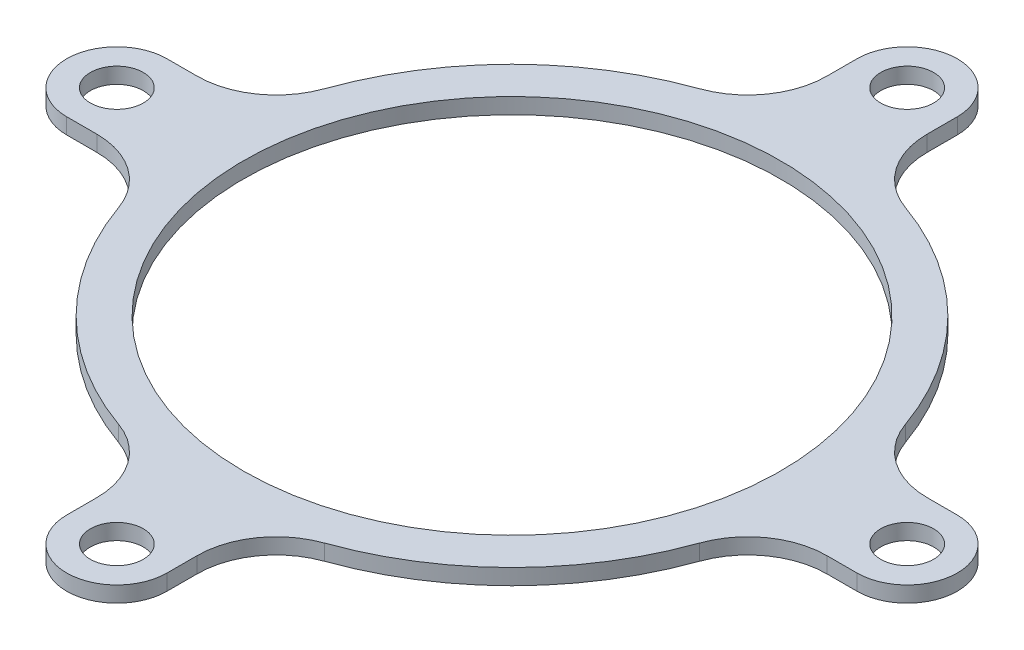
SolidWorks part; units mm, degrees
ref_plane "Front Plane" through (0, 0, 0) normal (0, 0, 1) x (1, 0, 0)
ref_plane "Top Plane" through (0, 0, 0) normal (0, 1, 0) x (1, 0, 0)
ref_plane "Right Plane" through (0, 0, 0) normal (1, 0, 0) x (0, 0, -1)
sketch "Sketch1" plane through (0, 0, 0) normal (0, 1, 0) x (1, 0, 0)
  circle A0 centre (0, 0) radius 34
  circle A1 centre (0, 0) radius 39
  dimension "innerDiam" = 68
  dimension "outerDiam" = 78
extrude "Boss-Extrude1" add sketch "Sketch1" along normal mid plane 2
sketch "Sketch2" plane through (0, 1, 0) normal (0, 1, 0) x (1, 0, 0)
  line L0 (0, 0) -> (0, 38.8704) construction
  line L1 (-6.35, 46.1917) -> (-6.35, 50)
  line L2 (6.35, 50) -> (6.35, 46.1917)
  arc A0 (-6.35, 50) -> (6.35, 50) centre (0, 50) cw
  arc A1 (6.35, 46.1917) -> (13.0133, 36.7649) centre (16.35, 46.1917) ccw
  circle A2 centre (0, 0) radius 39 construction
  arc A3 (-6.35, 46.1917) -> (-13.0133, 36.7649) centre (-16.35, 46.1917) cw
  arc A4 (13.0133, 36.7649) -> (-13.0133, 36.7649) centre (0, 0) ccw
  circle A5 centre (0, 0) radius 50 construction
  circle A6 centre (0, 50) radius 3.35
  point P15 (0, 0)
  point P16 (0, 0)
  dimension "supportsDiam" = 100
  dimension "rodDiam" = 6.7
  dimension "D3" = 3
  dimension "D4" = 10
extrude "Boss-Extrude2" add sketch "Sketch2" against normal up to surface (2 mm away) up to face at (0, -1, 39)
pattern_circular "CirPattern1" count 4 over 360 about axis through (0, 1, 0) along (0, -1, 0) of "Boss-Extrude2" reverse direction yes
